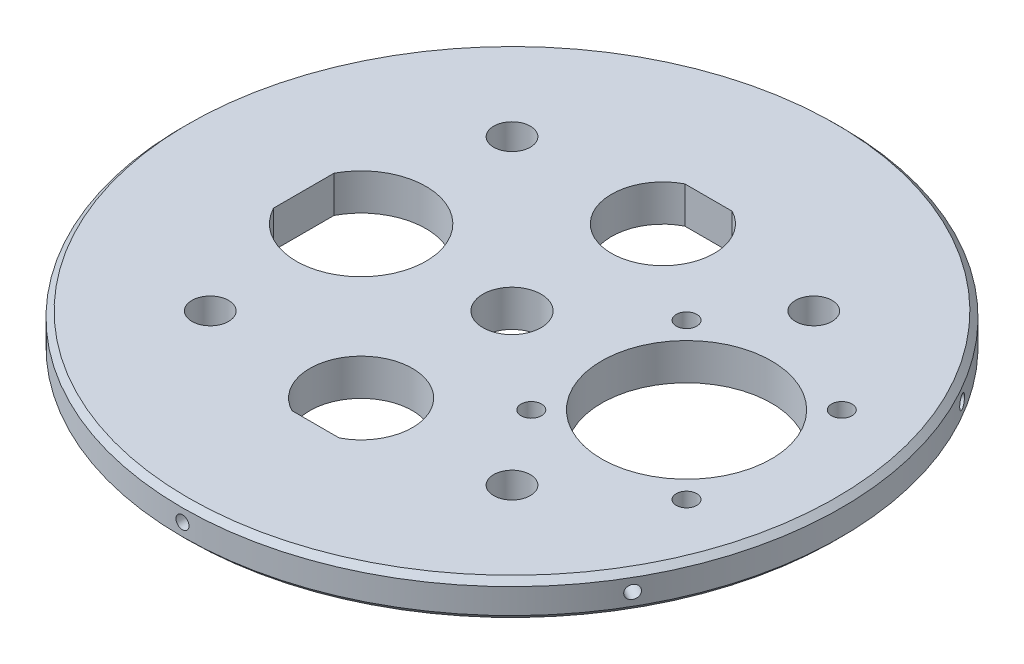
SolidWorks part; units mm, degrees
ref_plane "Front Plane" through (0, 0, 0) normal (0, 0, 1) x (1, 0, 0)
ref_plane "Top Plane" through (0, 0, 0) normal (0, 1, 0) x (1, 0, 0)
ref_plane "Right Plane" through (0, 0, 0) normal (1, 0, 0) x (0, 0, -1)
sketch "Sketch2" plane through (0, 0, 0) normal (0, 1, 0) x (1, 0, 0)
  circle A0 centre (0, 0) radius 57.15
  dimension "D1" = 114.3
extrude "Boss-Extrude1" add sketch "Sketch2" along normal blind 6.35 contours A0
sketch "Sketch6" plane through (0, 6.35, 0) normal (0, 1, 0) x (1, 0, 0)
  circle A0 centre (-26.1629, -26.1629) radius 3.175
  circle A1 centre (26.1629, -26.1629) radius 3.175
  circle A2 centre (-26.1629, 26.1631) radius 3.175
  circle A3 centre (26.1629, 26.1631) radius 3.175
  dimension "D1" = 6.35
  dimension "D2" = 74
  dimension "D3" = 26.1629
  dimension "D4" = 26.1629
  dimension "D5" = 26.1629
extrude "Cut-Extrude1" cut sketch "Sketch6" against normal up to next
sketch "Sketch7" plane through (0, 6.35, 0) normal (0, 1, 0) x (1, 0, 0)
  circle A0 centre (30, 0.2699) radius 14.732
  circle A3 centre (16.54, -13.1941) radius 1.778
  circle A4 centre (16.54, 13.7299) radius 1.778
  circle A5 centre (43.46, 13.7299) radius 1.778
  circle A6 centre (43.46, -13.1941) radius 1.778
  dimension "D1" = 29.464
  dimension "D2" = 3.556
  dimension "D3" = 3.556
  dimension "D4" = 3.556
  dimension "D5" = 3.556
  dimension "D6" = 13.46
  dimension "D7" = 13.46
  dimension "D8" = 13.46
  dimension "D9" = 13.464
  dimension "D10" = 30
extrude "Cut-Extrude2" cut sketch "Sketch7" against normal through all
sketch "Sketch8" plane through (0, 6.35, 0) normal (0, 1, 0) x (1, 0, 0)
  line L0 (4.0988, 34.0631) -> (-4.0988, 34.0631)
  line L1 (4.0988, -34.0629) -> (-4.0988, -34.0629)
  line L2 (-36.1129, 5.2498) -> (-36.1129, -5.2498)
  arc A0 (4.0988, -34.0629) -> (-4.0988, -34.0629) centre (0, -26.1629) ccw
  arc A1 (-4.0988, 34.0631) -> (4.0988, 34.0631) centre (0, 26.1631) ccw
  circle A2 centre (0, 0) radius 5.042
  arc A3 (-36.1129, -5.2498) -> (-36.1129, 5.2498) centre (-26.1629, 0) ccw
  circle A4 centre (26.1629, -26.1629) radius 3.175 construction
  circle A5 centre (26.1629, 26.1631) radius 3.175 construction
  circle A6 centre (-26.1629, -26.1629) radius 3.175 construction
  dimension "D1" = 17.8
  dimension "D2" = 17.8
  dimension "D3" = 10.084
  dimension "D4" = 22.5
  dimension "D5" = 7.9
  dimension "D6" = 0
  dimension "D7" = 7.9
  dimension "D8" = 0
  dimension "D9" = 9.95
  dimension "D10" = 0
extrude "Cut-Extrude3" cut sketch "Sketch8" against normal through all
sketch "Sketch10" plane through (0, 6.35, 0) normal (0, 1, 0) x (1, 0, 0)
  circle A0 centre (-26.1629, 26.1631) radius 7.9375
  circle A1 centre (26.1631, 26.1629) radius 7.9375
  circle A2 centre (26.1629, -26.1631) radius 7.9375
  circle A3 centre (-26.1631, -26.1629) radius 7.9375
  point P11 (0, 0)
  dimension "D1" = 4
sketch "Sketch11" plane through (0, 6.35, 0) normal (0, 1, 0) x (1, 0, 0)
  circle A0 centre (0, 0) radius 10
ref_plane "Plane1" through (0, 0, -57.15) normal (0, 0, -1) x (-1, 0, 0)
sketch "Sketch12" plane through (0, 0, -57.15) normal (0, 0, -1) x (-1, 0, 0)
  line L0 (57.15, 0) -> (57.15, 6.35) construction
  point P0 (0, 3.175)
  point P1 (57.15, 3.175)
hole_wizard "#4-40 Tapped Hole2" positions "3DSketch7" profile "Sketch16" tap size "#4-40" standard "ANSI Inch"
sketch3d "3DSketch7"
  point P0 (0, 3.175, -57.15)
sketch "Sketch16" plane through (0, 3.175, -57.15) normal (1, 0, 0) x (0, 1, 0)
  line L0 (0, 0) -> (0, 10.6792)
  line L1 (0, 10.6792) -> (1.1303, 10)
  line L2 (1.1303, 10) -> (1.1303, 0)
  line L5 (1.1303, 0) -> (0, 0)
  line L10 (0, 10.6792) -> (-1.1303, 10) construction
  line L11 (0, -6.35) -> (0, 107.95) construction
  dimension "Tap Drill Dia." = 2.2606
  dimension "Tap Drill Depth" = 10
  dimension "Drill Angle" = 118
cosmetic thread "Hole Thread2" parameters "D1"=5.69, "D2"=2.8448
pattern_circular "CirPattern1" count 6 over 360 about axis through (0, 0, 0) along (0, 1, 0) of "#4-40 Tapped Hole2"
cosmetic thread "Hole Thread3" parameters "D1"=5.69, "D2"=2.8448
cosmetic thread "Hole Thread4" parameters "D1"=5.69, "D2"=2.8448
cosmetic thread "Hole Thread5" parameters "D1"=5.69, "D2"=2.8448
cosmetic thread "Hole Thread6" parameters "D1"=5.69, "D2"=2.8448
cosmetic thread "Hole Thread7" parameters "D1"=5.69, "D2"=2.8448
cosmetic thread "Hole Thread8" parameters "D1"=5.69, "D2"=2.8448
cosmetic thread "Hole Thread9" parameters "D1"=5.69, "D2"=2.8448
chamfer "Chamfer1" distance 1 angle 45 2 edges at (0, 6.35, 57.15) (0, 0, 57.15)
equation "\"width\"=26.1629"
equation "\"D4@Sketch6\"=\"width\""
equation "\"D3@Sketch6\"=\"width\""
equation "\"D5@Sketch6\"=\"width\""
